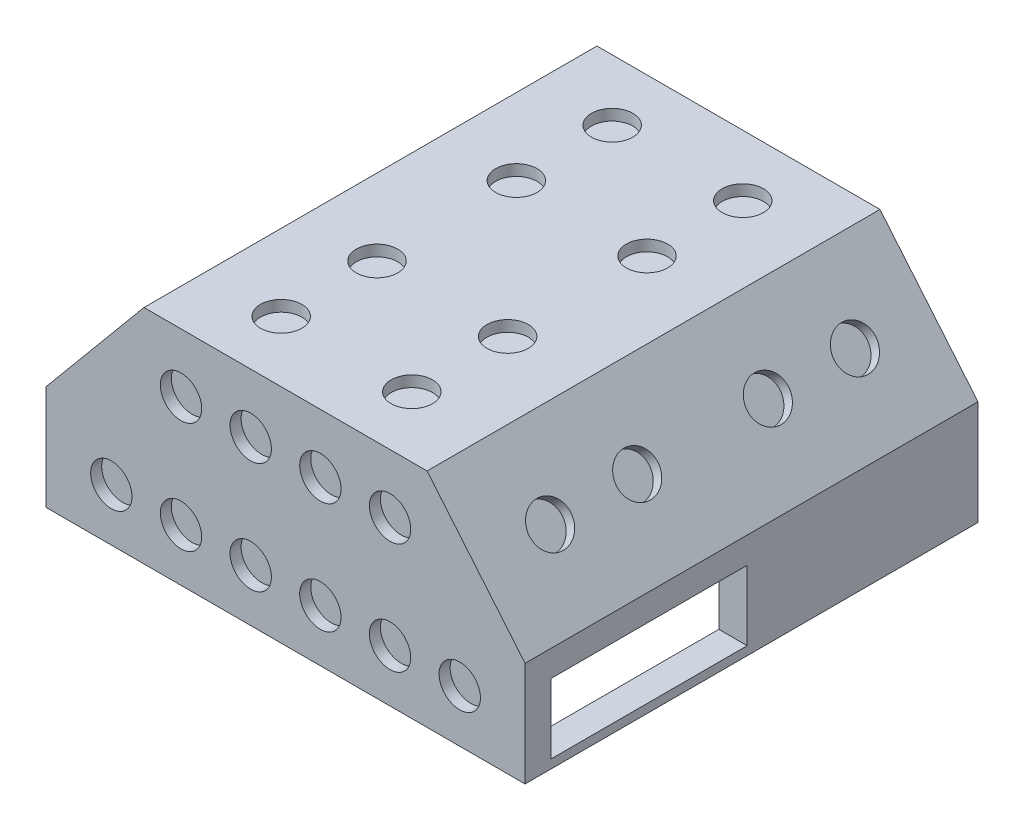
SolidWorks part; units mm, degrees
ref_plane "Alzado" through (0, 0, 0) normal (0, 0, 1) x (1, 0, 0)
ref_plane "Planta" through (0, 0, 0) normal (0, 1, 0) x (1, 0, 0)
ref_plane "Vista lateral" through (0, 0, 0) normal (1, 0, 0) x (0, 0, -1)
sketch "Croquis2" plane through (0, 0, 0) normal (0, 0, 1) x (1, 0, 0)
  line L0 (-55, 0) -> (-32.5, 0)
  line L1 (-32.5, 0) -> (-32.5, 27)
  line L2 (-32.5, 27) -> (-55, 0)
  line L3 (32.5, 27) -> (55, 0)
  line L4 (-32.5, 27) -> (32.5, 27)
  line L5 (-32.5, 27) -> (-32.5, 0)
  line L6 (-32.5, 0) -> (32.5, 0)
  line L7 (32.5, 27) -> (32.5, 0)
  line L8 (55, 0) -> (32.5, 0)
  dimension "D1" = 110
  dimension "D2" = 65
  dimension "D3" = 27
extrude "Saliente-Extruir1" add sketch "Croquis2" along normal blind 104 contours L7 L4 L1 L6 | L1 L2 L0 | L8 L3 L7 region at (-40, 9, 0) region at (0, 13.5, 0) region at (40, 9, 0)
sketch "Croquis3" plane through (0, 0, 0) normal (0, 0, -1) x (-1, 0, 0)
  line L0 (-48.4915, 0) -> (-28.6581, 23.8)
  line L1 (55, 0) -> (-55, 0) construction
  line L2 (-28.6581, 23.8) -> (28.6581, 23.8)
  line L3 (28.6581, 23.8) -> (48.4915, 0)
  line L4 (48.4915, 0) -> (-48.4915, 0)
  line L5 (-32.5, 27) -> (-55, 0) construction
  line L6 (32.5, 27) -> (-32.5, 27) construction
  line L9 (32.5, 27) -> (55, 0) construction
  line L11 (55, 0) -> (48.4915, 0)
  line M1 (-55, 0) -> (55, 0)
  dimension "D1" = 5
  dimension "D2" = 5
  dimension "D3" = 3.2
extrude "Cortar-Extruir1" cut sketch "Croquis3" against normal blind 98 contours L3 L2 L0 M1 region at (0, 10.8803, 0)
sketch "Croquis13" plane through (0, 27, 0) normal (0, 1, 0) x (1, 0, 0)
  line L0 (0, 0) -> (0, -104) construction
  line L1 (-32.5, 0) -> (32.5, 0) construction
  line L2 (-32.5, -104) -> (32.5, -104) construction
  circle A0 centre (-15, -14) radius 4.75
  circle A1 centre (-15, -36) radius 4.75
  circle A2 centre (-15, -68) radius 4.75
  circle A3 centre (-15, -90) radius 4.75
  circle A4 centre (15, -14) radius 4.75
  circle A5 centre (15, -36) radius 4.75
  circle A6 centre (15, -68) radius 4.75
  circle A7 centre (15, -90) radius 4.75
  dimension "D1" = 9.5
  dimension "D2" = 14
  dimension "D3" = 22
  dimension "D4" = 14
  dimension "D5" = 22
  dimension "D6" = 32
  dimension "D7" = 15
extrude "Cortar-Extruir3" cut sketch "Croquis13" against normal blind 2.54
sketch "Croquis14" plane through (-32.459, 27.0492, 0) normal (-0.7682, 0.6402, 0) x (0, 0, 1)
  line L0 (0, -17.6371) -> (104, -17.6371) construction
  line L1 (0, -0.064) -> (0, -35.2101) construction
  line L2 (104, -0.064) -> (104, -35.2101) construction
  circle A0 centre (17, -17.6371) radius 4.75
  circle A1 centre (37, -17.6371) radius 4.75
  circle A2 centre (67, -17.6371) radius 4.75
  circle A3 centre (87, -17.6371) radius 4.75
  dimension "D1" = 9.5
  dimension "D2" = 17
  dimension "D3" = 20
  dimension "D4" = 17
  dimension "D5" = 20
  dimension "D6" = 30
extrude "Cortar-Extruir4" cut sketch "Croquis14" against normal blind 2.54
sketch "Croquis15" plane through (32.459, 27.0492, 0) normal (0.7682, 0.6402, 0) x (0, 0, -1)
  line L0 (0, -17.6371) -> (-104, -17.6371) construction
  line L1 (0, -0.064) -> (0, -35.2101) construction
  line L2 (-104, -0.064) -> (-104, -35.2101) construction
  circle A0 centre (-17, -17.6371) radius 4.75
  circle A1 centre (-37, -17.6371) radius 4.75
  circle A2 centre (-87, -17.6371) radius 4.75
  circle A3 centre (-67, -17.6371) radius 4.75
  dimension "D1" = 9.5
  dimension "D2" = 17
  dimension "D3" = 20
  dimension "D4" = 20
  dimension "D5" = 17
extrude "Cortar-Extruir5" cut sketch "Croquis15" against normal blind 2.54
sketch "Croquis17" plane through (0, 0, 104) normal (0, 0, 1) x (1, 0, 0)
  line L0 (0, 27) -> (0, 0) construction
  line L1 (-32.5, 27) -> (32.5, 27) construction
  line L2 (-55, 0) -> (55, 0) construction
  line L3 (-43.75, 13.5) -> (43.75, 13.5) construction
  line L4 (-32.5, 27) -> (-55, 0) construction
  line L5 (32.5, 27) -> (55, 0) construction
  circle A0 centre (-8, 13.5) radius 4.75
  circle A1 centre (8, 13.5) radius 4.75
  circle A2 centre (-24, 13.5) radius 4.75
  circle A3 centre (24, 13.5) radius 4.75
  dimension "D1" = 9.5
  dimension "D2" = 8
  dimension "D3" = 16
extrude "Cortar-Extruir7" cut sketch "Croquis17" against normal blind 2.54
sketch "Croquis18" plane through (0, 0, 0) normal (0, -1, 0) x (1, 0, 0)
  line L1 (-55, 0) -> (-48.4915, 0)
  line L2 (-55, 0) -> (-55, 104)
  line L3 (-48.4915, 98) -> (-48.4915, 0) construction
  line L4 (-48.4915, 0) -> (-48.4915, 98)
  line L5 (-55, 104) -> (55, 104)
  line L7 (48.4915, 98) -> (48.4915, 0) construction
  line L9 (-55, 104) -> (-55, 0) construction
  line L10 (55, 0) -> (48.4915, 0)
  line L11 (55, 0) -> (55, 104)
  line L12 (48.4915, 98) -> (-48.4915, 98) construction
  line L13 (48.4915, 0) -> (48.4915, 98)
  line L15 (55, 104) -> (55, 0) construction
  line L16 (-48.4915, 98) -> (48.4915, 98)
  line M1 (-48.4915, 0) -> (-48.4915, 98)
  line M3 (-48.4915, 0) -> (-48.4915, 98)
  line M5 (-48.4915, 0) -> (-48.4915, 98)
  line M6 (-48.4915, 98) -> (48.4915, 98)
  line M7 (48.4915, 98) -> (48.4915, 0)
  line M9 (48.4915, 98) -> (48.4915, 0)
  line M11 (48.4915, 98) -> (48.4915, 0)
  line M12 (48.4915, 0) -> (55, 0)
  line M13 (55, 0) -> (55, 104)
  line M14 (55, 104) -> (-55, 104)
  line M15 (-55, 104) -> (-55, 0)
  line M16 (-55, 0) -> (-48.4915, 0)
extrude "Saliente-Extruir2" add sketch "Croquis18" along normal blind 24 contours M15 M16 M1 M3 M5 | M6 M13 M14 M15 | M7 M9 M11 M12 M13 region at (-53.4862, 0, 52)
sketch "Croquis19" plane through (55, 0, 0) normal (1, 0, 0) x (0, 0, -1)
  line L0 (0, -24) -> (-104, -24) construction
  line L1 (-98, -6) -> (-53, -6)
  line L2 (-98, -6) -> (-98, -22)
  line L3 (-98, -22) -> (-53, -22)
  line L4 (-53, -6) -> (-53, -22)
  line L5 (-104, 0) -> (0, 0) construction
  line L6 (-104, -24) -> (-104, 0) construction
  dimension "D1" = 45
  dimension "D2" = 2
  dimension "D3" = 6
  dimension "D4" = 6
extrude "Cortar-Extruir8" cut sketch "Croquis19" against normal up to surface (110 mm away) up to face at (-55, -12, 52)
sketch "Croquis20" plane through (48.4915, 0, 0) normal (-1, 0, 0) x (0, 0, 1)
  line L0 (0, -24) -> (0, 0) construction
  line L1 (98, 0) -> (0, 0)
  line L2 (98, 0) -> (98, -3)
  line L3 (98, -3) -> (0, -3)
  line L4 (0, 0) -> (0, -3)
  dimension "D1" = 3
extrude "Saliente-Extruir3" add sketch "Croquis20" along normal up to next
sketch "Croquis22" plane through (0, 0, 0) normal (0, 0, -1) x (-1, 0, 0)
  line L0 (-38.4915, 0) -> (-38.4915, 12)
  line L1 (48.4915, 0) -> (-48.4915, 0) construction
  line L2 (-48.4915, 0) -> (-28.6581, 23.8) construction
  line L3 (38.4915, 12) -> (38.4915, 0)
  line L4 (28.6581, 23.8) -> (48.4915, 0) construction
  line L5 (-38.4915, 0) -> (-48.4915, 0)
  line L6 (-48.4915, 0) -> (-38.4915, 12)
  line L7 (38.4915, 0) -> (48.4915, 0)
  line L8 (48.4915, 0) -> (38.4915, 12)
  dimension "D1" = 10
  dimension "D2" = 10
extrude "Saliente-Extruir4" add sketch "Croquis22" against normal up to next
sketch "Croquis25" plane through (0, -24, 0) normal (0, -1, 0) x (1, 0, 0)
  line L0 (-55, 100) -> (55, 100) construction
  line L2 (55, 0) -> (55, 104) construction
  line L3 (-51.7457, 104) -> (-51.7457, 0) construction
  line L4 (55, 104) -> (-55, 104) construction
  line L5 (-55, 0) -> (-48.4915, 0) construction
  line L6 (51.7457, 104) -> (51.7457, 0) construction
  line L7 (48.4915, 0) -> (55, 0) construction
  line L9 (-55, 4) -> (55, 4) construction
  line L10 (-55, 104) -> (-55, 0) construction
  dimension "D1" = 4
  dimension "D2" = 4
hole_wizard "Taladro de margen para M31" positions "Croquis3D1" profile "Croquis26" hole size "M3" standard "ISO"
sketch3d "Croquis3D1"
  line L0 (-55, -24, 100) -> (55, -24, 100) construction
  line L1 (-51.7457, -24, 104) -> (-51.7457, -24, 0) construction
  line L2 (51.7457, -24, 104) -> (51.7457, -24, 0) construction
  line L3 (-55, -24, 4) -> (55, -24, 4) construction
  point P0 (-51.7457, -24, 100)
  point P6 (51.7457, -24, 100)
  point P10 (51.7457, -24, 4)
  point P14 (-51.7457, -24, 4)
sketch "Croquis26" plane through (-51.7457, -24, 100) normal (1, 0, 0) x (0, 0, -1)
  line L0 (0, 0) -> (0, 10.9614)
  line L1 (0, 10.9614) -> (1.6, 10)
  line L2 (1.6, 10) -> (1.6, 0)
  line L5 (1.6, 0) -> (0, 0)
  line L10 (0, 10.9614) -> (-1.6, 10) construction
  line L11 (0, -6.35) -> (0, 107.95) construction
  dimension "Diámetro de taladro" = 3.2
  dimension "Profundidad de taladro" = 10
  dimension "Ángulo de perforador" = 118
sketch "Croquis27" plane through (0, 0, 0) normal (0, 0, -1) x (-1, 0, 0)
  line L0 (-53.3333, 2) -> (53.3333, 2) construction
  line L1 (-32.5, 27) -> (-55, 0) construction
  line L2 (32.5, 27) -> (55, 0) construction
  line L3 (-44.4915, -3) -> (-44.4915, 12.6102) construction
  line L4 (48.4915, -3) -> (-48.4915, -3) construction
  line L5 (44.4915, -3) -> (44.4915, 12.6102) construction
  line L6 (48.4915, -3) -> (-48.4915, -3) construction
  line L7 (38.4915, 12) -> (38.4915, 0) construction
  line L9 (-38.4915, 0) -> (-38.4915, 12) construction
  point P16 (-38.4915, 6)
  dimension "D1" = 5
  dimension "D2" = 6
  dimension "D3" = 6
hole_wizard "Taladro de margen para M33" positions "Croquis3D4" profile "Croquis30" hole size "M3" standard "ISO"
sketch3d "Croquis3D4"
  line L0 (53.3333, 2, 0) -> (-53.3333, 2, 0) construction
  line L1 (44.4915, -3, 0) -> (44.4915, 12.6102, 0) construction
  line L2 (-44.4915, -3, 0) -> (-44.4915, 12.6102, 0) construction
  point P0 (44.4915, 2, 0)
  point P6 (-44.4915, 2, 0)
sketch "Croquis30" plane through (44.4915, 2, 0) normal (1, 0, 0) x (0, 1, 0)
  line L0 (0, 0) -> (0, 5.9614)
  line L1 (0, 5.9614) -> (1.6, 5)
  line L2 (1.6, 5) -> (1.6, 0)
  line L5 (1.6, 0) -> (0, 0)
  line L10 (0, 5.9614) -> (-1.6, 5) construction
  line L11 (0, -6.35) -> (0, 107.95) construction
  dimension "Diámetro de taladro" = 3.2
  dimension "Profundidad de taladro" = 5
  dimension "Ángulo de perforador" = 118
sketch "Croquis32" plane through (0, 0, 104) normal (0, 0, 1) x (1, 0, 0)
  line L0 (-55, -12) -> (55, -12) construction
  line L1 (-55, -24) -> (-55, 0) construction
  line L2 (55, -24) -> (55, 0) construction
  line L3 (0, 27) -> (0, -24) construction
  line L4 (-32.5, 27) -> (32.5, 27) construction
  line L5 (55, -24) -> (-55, -24) construction
  circle A0 centre (-8, -12) radius 4.75
  circle A1 centre (-24, -12) radius 4.75
  circle A2 centre (8, -12) radius 4.75
  circle A3 centre (24, -12) radius 4.75
  circle A4 centre (-40, -12) radius 4.75
  circle A5 centre (40, -12) radius 4.75
  dimension "D1" = 9.5
  dimension "D2" = 16
  dimension "D3" = 16
  dimension "D4" = 8
  dimension "D5" = 8
  dimension "D6" = 16
  dimension "D7" = 16
extrude "Cortar-Extruir9" cut sketch "Croquis32" against normal blind 2.54
